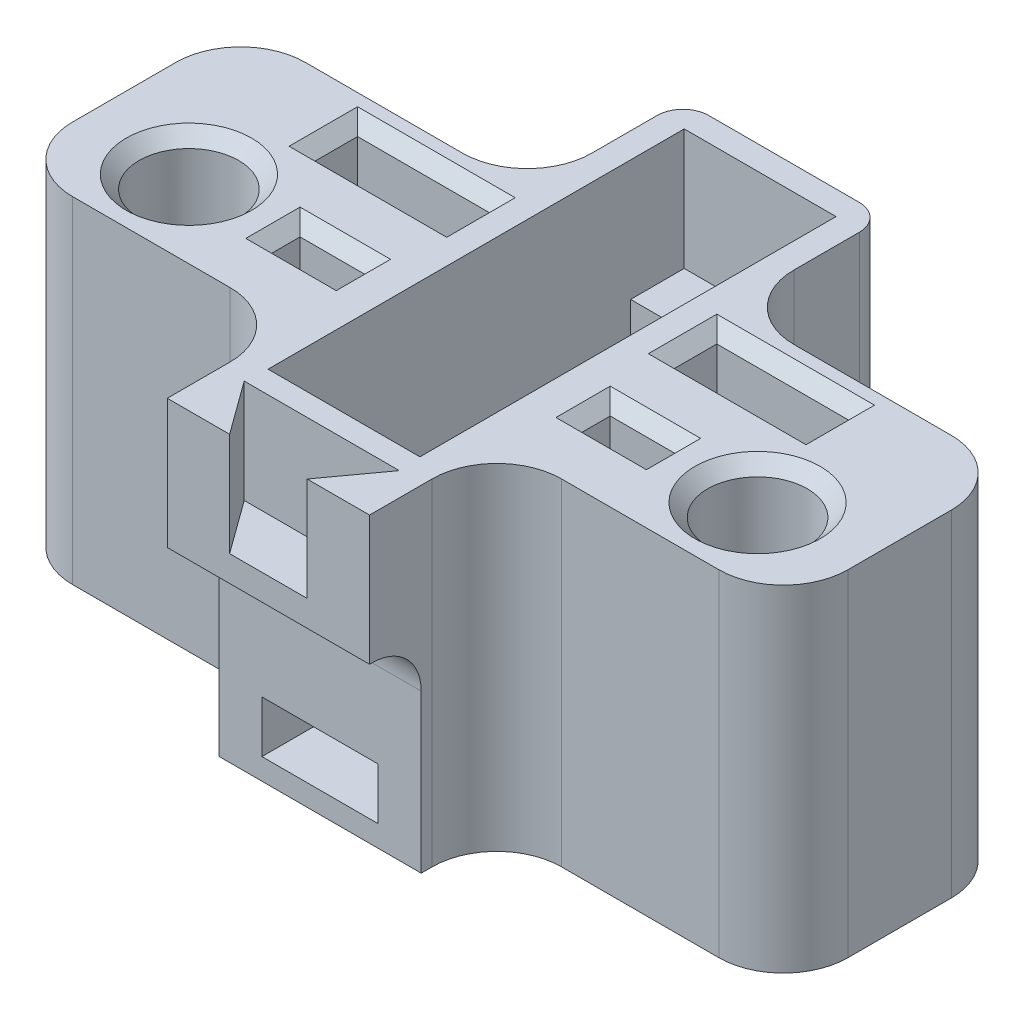
SolidWorks part; units mm, degrees
ref_plane "Front Plane" through (0, 0, 0) normal (0, 0, 1) x (1, 0, 0)
ref_plane "Top Plane" through (0, 0, 0) normal (0, 1, 0) x (1, 0, 0)
ref_plane "Right Plane" through (0, 0, 0) normal (1, 0, 0) x (0, 0, -1)
sketch "Sketch1" plane through (0, 0, 0) normal (0, 1, 0) x (1, 0, 0)
  line L1 (-30, -9) -> (30, -9)
  line L2 (-30, -9) -> (-30, 9)
  line L3 (-30, 9) -> (30, 9)
  line L4 (30, -9) -> (30, 9)
  line L5 (-30, -9) -> (30, 9) construction
  line L6 (-30, 9) -> (30, -9) construction
  point P0 (0, 0)
  dimension "D1" = 60
  dimension "D2" = 18
extrude "Boss-Extrude1" add sketch "Sketch1" along normal blind 26
sketch "Sketch2" plane through (0, 26, 0) normal (0, 1, 0) x (1, 0, 0)
  line L0 (0, 0) -> (0, -9) construction
  line L1 (-30, -9) -> (30, -9) construction
  circle A0 centre (-22, -3) radius 3.85
  circle A1 centre (22, -3) radius 3.85
  dimension "D1" = 7.7
  dimension "D2" = 7.7
  dimension "D3" = 44
  dimension "D4" = 22
  dimension "D5" = 6
  dimension "D6" = 6
extrude "Eyeshaft holes" cut sketch "Sketch2" against normal blind 15
fillet "Eyeshaft Fillet" radius 3 2 edges at (22, 11, 6.85) (-22, 11, 6.85)
sketch "Sketch5" plane through (0, 26, 0) normal (0, 1, 0) x (1, 0, 0)
  line L0 (-22, -3) -> (22, -3) construction
  line L2 (-14.5, -4.1) -> (-9.5, -4.1)
  line L3 (-14.5, -4.1) -> (-14.5, -1.9)
  line L4 (-14.5, -1.9) -> (-9.5, -1.9)
  line L5 (-9.5, -4.1) -> (-9.5, -1.9)
  line L6 (-14.5, -4.1) -> (-9.5, -1.9) construction
  line L7 (-14.5, -1.9) -> (-9.5, -4.1) construction
  line L8 (9.5, -4.1) -> (14.5, -4.1)
  line L9 (9.5, -4.1) -> (9.5, -1.9)
  line L10 (9.5, -1.9) -> (14.5, -1.9)
  line L11 (14.5, -4.1) -> (14.5, -1.9)
  line L12 (9.5, -4.1) -> (14.5, -1.9) construction
  line L13 (9.5, -1.9) -> (14.5, -4.1) construction
  point P4 (-12, -3)
  point P9 (12, -3)
  dimension "D1" = 2.2
  dimension "D2" = 5
  dimension "D3" = 5
  dimension "D4" = 2.2
  dimension "D5" = 10
  dimension "D6" = 10
extrude "Front leg holes" cut sketch "Sketch5" against normal blind 13
sketch "Sketch7" plane through (0, 26, 0) normal (0, 1, 0) x (1, 0, 0)
  line L1 (-19, 7.05) -> (-8.8, 7.05)
  line L2 (-19, 7.05) -> (-19, 3.75)
  line L3 (-19, 3.75) -> (-8.8, 3.75)
  line L4 (-8.8, 7.05) -> (-8.8, 3.75)
  line L5 (8.8, 7.05) -> (19, 7.05)
  line L6 (8.8, 7.05) -> (8.8, 3.75)
  line L7 (8.8, 3.75) -> (19, 3.75)
  line L8 (19, 7.05) -> (19, 3.75)
  circle A0 centre (-22, -3) radius 3.85 construction
  circle A2 centre (22, -3) radius 3.85 construction
  point P16 (-20.2379, 3.75)
  dimension "D1" = 3.3
  dimension "D2" = 10.2
  dimension "D3" = 10.2
  dimension "D4" = 3.3
  dimension "D5" = 10.05
  dimension "D6" = 10.05
  dimension "D7" = 3
  dimension "D8" = 3
extrude "Back Legs" cut sketch "Sketch7" against normal blind 13
sketch "Sketch18" plane through (0, 26, 0) normal (0, 1, 0) x (1, 0, 0)
  line L0 (0, 9) -> (0, -9) construction
  line L1 (30, 9) -> (-30, 9) construction
  line L2 (-30, -9) -> (30, -9) construction
  line L3 (-22, -3) -> (22, -3) construction
  line L4 (-7.825, -14.85) -> (7.825, -14.85)
  line L5 (-7.825, -14.85) -> (-7.825, 21.05)
  line L6 (-7.825, 21.05) -> (7.825, 21.05)
  line L7 (7.825, -14.85) -> (7.825, 21.05)
  line L8 (-7.825, -14.85) -> (7.825, 21.05) construction
  line L9 (-7.825, 21.05) -> (7.825, -14.85) construction
  point P6 (0, 3.1)
  dimension "D1" = 24.05
  dimension "D2" = 11.85
  dimension "D3" = 15.65
extrude "Servo Block" add sketch "Sketch18" against normal up to surface (26 mm away) up to face at (0, 0, 0)
sketch "Sketch19" plane through (0, 26, 0) normal (0, 1, 0) x (1, 0, 0)
  line L0 (0, 21.05) -> (0, -14.85) construction
  line L1 (7.825, 21.05) -> (-7.825, 21.05) construction
  line L2 (-7.825, -14.85) -> (7.825, -14.85) construction
  line L3 (-22, -3) -> (22, -3) construction
  line L5 (-5.875, -13) -> (5.875, -13)
  line L6 (-5.875, -13) -> (-5.875, 19.2)
  line L7 (-5.875, 19.2) -> (5.875, 19.2)
  line L8 (5.875, -13) -> (5.875, 19.2)
  line L9 (-5.875, -13) -> (5.875, 19.2) construction
  line L10 (-5.875, 19.2) -> (5.875, -13) construction
  point P10 (0, 3.1)
  dimension "D1" = 22.2
  dimension "D2" = 10
  dimension "D3" = 11.75
extrude "Servo Arms" cut sketch "Sketch19" against normal blind 9.35
sketch "Sketch20" plane through (0, 16.65, 0) normal (0, 1, 0) x (1, 0, 0)
  line L0 (-22, -3) -> (22, -3) construction
  line L1 (0, -13) -> (0, 19.2) construction
  line L2 (-5.875, -13) -> (5.875, -13) construction
  line L3 (5.875, 19.2) -> (-5.875, 19.2) construction
  line L5 (-5.875, 15.05) -> (5.875, 15.05)
  line L6 (-5.875, 15.05) -> (-5.875, -8.85)
  line L7 (-5.875, -8.85) -> (5.875, -8.85)
  line L8 (5.875, 15.05) -> (5.875, -8.85)
  line L9 (-5.875, 15.05) -> (5.875, -8.85) construction
  line L10 (-5.875, -8.85) -> (5.875, 15.05) construction
  point P10 (0, 3.1)
  dimension "D1" = 5.85
  dimension "D2" = 18.05
  dimension "D3" = 11.75
extrude "Cut-Extrude10" cut sketch "Sketch20" against normal blind 15
sketch "Sketch15" [suppressed] plane through (0, 0, 17.5) normal (0, 0, 1) x (1, 0, 0)
  line L0 (0, 0) -> (0, 26) construction
  line L1 (-10, 0) -> (10, 0) construction
  line L2 (10, 26) -> (-10, 26) construction
  line L4 (-4.5, 1.4) -> (4.5, 1.4)
  line L5 (-4.5, 1.4) -> (-4.5, 5.4)
  line L6 (-4.5, 5.4) -> (4.5, 5.4)
  line L7 (4.5, 1.4) -> (4.5, 5.4)
  line L8 (-4.5, 1.4) -> (4.5, 5.4) construction
  line L9 (-4.5, 5.4) -> (4.5, 1.4) construction
  point P6 (0, 3.4)
  dimension "D1" = 9
  dimension "D2" = 4
  dimension "D3" = 1.4
sketch "Sketch16" [suppressed] plane through (0, 12.4, 0) normal (0, 1, 0) x (1, 0, 0)
  line L0 (-6.1, -12) -> (6.1, -12) construction
  line L1 (-2.5, -12.5) -> (2.5, -12.5)
  line L2 (-2.5, -12.5) -> (-2.5, -11.5)
  line L3 (-2.5, -11.5) -> (2.5, -11.5)
  line L4 (2.5, -12.5) -> (2.5, -11.5)
  line L5 (-2.5, -12.5) -> (2.5, -11.5) construction
  line L6 (-2.5, -11.5) -> (2.5, -12.5) construction
  point P0 (0, -12)
  dimension "D1" = 5
  dimension "D2" = 1
sketch "Sketch13" [suppressed] plane through (0, 12.4, 0) normal (0, 1, 0) x (1, 0, 0)
  line L1 (6.1, 13) -> (6.1, 16.6) construction
  line L2 (6.1, 13) -> (-6.1, 13) construction
  line L4 (6.1, -16.6) -> (6.1, -12) construction
  line L5 (-2.5, -12.5) -> (2.5, -12.5) construction
  circle A0 centre (0.1, 15) radius 0.5
  circle A1 centre (0.1, -14.5) radius 0.5
  dimension "D2" = 6
  dimension "D3" = 1
  dimension "D4" = 1
  dimension "D1" = 2
  dimension "D5" = 2
  dimension "D6" = 6
fillet "Fillet3" [suppressed] radius 2
sketch "Sketch17" plane through (0, 26, 0) normal (0, 1, 0) x (1, 0, 0)
  line L1 (-5.9, -16.2) -> (5.9, -16.2)
  line L2 (-5.9, -16.2) -> (-5.9, 16.2)
  line L3 (-5.9, 16.2) -> (5.9, 16.2)
  line L4 (5.9, -16.2) -> (5.9, 16.2)
  line L5 (-5.9, -16.2) -> (5.9, 16.2) construction
  line L6 (-5.9, 16.2) -> (5.9, -16.2) construction
  point P0 (0, 0)
  dimension "D1" = 11.8
  dimension "D2" = 32.4
extrude "Servo Body" [suppressed] cut sketch "Sketch17" against normal blind 24
ref_axis "Axis1" through (-22, 14, 3) along (0, 1, 0)
ref_axis "Axis2" through (22, 14, 3) along (0, 1, 0)
ref_plane "Plane2" through (0, 0, 3) normal (0, 0, 1) x (1, 0, 0)
fillet "Fillet4" radius 5 4 edges at (30, 13, -9) (30, 13, 9) (-30, 13, 9) (-30, 13, -9)
chamfer "Chamfer1" distance 1 angle 45 18 edges at (22, 26, 6.85) (-22, 26, 6.85) (-14.5, 26, 3) (-12, 26, 4.1) (-12, 26, 1.9) (-9.5, 26, 3) (14.5, 26, 3) (12, 26, 4.1) (9.5, 26, 3) (12, 26, 1.9) (19, 26, -5.4) (13.9, 26, -3.75) (8.8, 26, -5.4) (13.9, 26, -7.05) (-8.8, 26, -5.4) (-13.9, 26, -3.75) (-19, 26, -5.4) (-13.9, 26, -7.05)
sketch "Sketch21" plane through (0, 0, 8.85) normal (0, 0, -1) x (-1, 0, 0)
  line L0 (0, 1.65) -> (0, 16.65) construction
  line L1 (5.875, 1.65) -> (-5.875, 1.65) construction
  line L2 (5.875, 16.65) -> (-5.875, 16.65) construction
  line L3 (4.5, 5.65) -> (-4.5, 5.65)
  line L4 (4.5, 5.65) -> (4.5, 1.65)
  line L5 (-4.5, 5.65) -> (-4.5, 1.65)
  line L6 (4.5, 1.65) -> (-4.5, 1.65)
  line L7 (4.5, 5.65) -> (-4.5, 1.65) construction
  line L8 (-4.5, 5.65) -> (4.5, 1.65) construction
  point P7 (0, 3.65)
  dimension "D1" = 9
  dimension "D2" = 0
  dimension "D3" = 4
  dimension "D4" = 0
extrude "Cut-Extrude11" cut sketch "Sketch21" against normal blind 15
fillet "Fillet5" radius 3 1 edges at (0, 5.65, 8.85)
sketch "Sketch22" plane through (0, 16.65, 0) normal (0, 1, 0) x (1, 0, 0)
  line L0 (5.875, 15.05) -> (-5.875, 15.05) construction
  line L1 (-5.875, -8.85) -> (5.875, -8.85) construction
  circle A0 centre (0, 17.3) radius 0.75
  circle A1 centre (0, -11.1) radius 0.75
  dimension "D1" = 2.25
  dimension "D2" = 1.5
  dimension "D3" = 1.5
  dimension "D4" = 2.25
extrude "Cut-Extrude12" cut sketch "Sketch22" against normal blind 3
fillet "Fillet6" radius 5 4 edges at (-7.825, 13, 9) (7.825, 13, 9) (7.825, 13, -9) (-7.825, 13, -9)
sketch "Sketch23" plane through (0, 0, 14.85) normal (0, 0, 1) x (1, 0, 0)
  line L0 (0, 26) -> (0, 5.65) construction
  line L1 (-7.825, 26) -> (7.825, 26) construction
  line L2 (4.5, 5.65) -> (-4.5, 5.65) construction
  line L4 (-7.825, 16) -> (7.825, 16)
  line L5 (-7.825, 16) -> (-7.825, 26)
  line L6 (-7.825, 26) -> (7.825, 26)
  line L7 (7.825, 16) -> (7.825, 26)
  line L8 (-7.825, 16) -> (7.825, 26) construction
  line L9 (-7.825, 26) -> (7.825, 16) construction
  point P6 (0, 21)
  dimension "D1" = 10
extrude "Boss-Extrude3" add sketch "Sketch23" along normal blind 4
sketch "Sketch24" plane through (0, 26, 0) normal (0, 1, 0) x (1, 0, 0)
  line L0 (7.825, -18.85) -> (-7.825, -18.85) construction
  line L1 (-6, -22.9791) -> (6, -22.9791)
  line L2 (-6, -22.9791) -> (-6, -14.7209)
  line L3 (-6, -14.7209) -> (6, -14.7209)
  line L4 (6, -22.9791) -> (6, -14.7209)
  line L5 (-6, -22.9791) -> (6, -14.7209) construction
  line L6 (-6, -14.7209) -> (6, -22.9791) construction
  line L7 (-6, -14.7209) -> (-3, -18.85)
  line L8 (-3, -18.85) -> (3, -18.85)
  line L9 (3, -18.85) -> (6, -14.7209)
  point P0 (0, -18.85)
  line M41 (-7.825, -18.85) -> (7.825, -18.85)
  dimension "D1" = 6
  dimension "D2" = 126
  dimension "D3" = 126
  dimension "D4" = 12
extrude "Dove tail" cut sketch "Sketch24" against normal blind 8 contours L9 L3 L7 M41 region at (0, 26, 16.556)
fillet "Fillet7" [suppressed] radius 1
fillet "Fillet8" radius 3.8 1 edges at (0, 16, 14.85)
fillet "Fillet9" radius 2 2 edges at (7.825, 13, -21.05) (-7.825, 13, -21.05)
